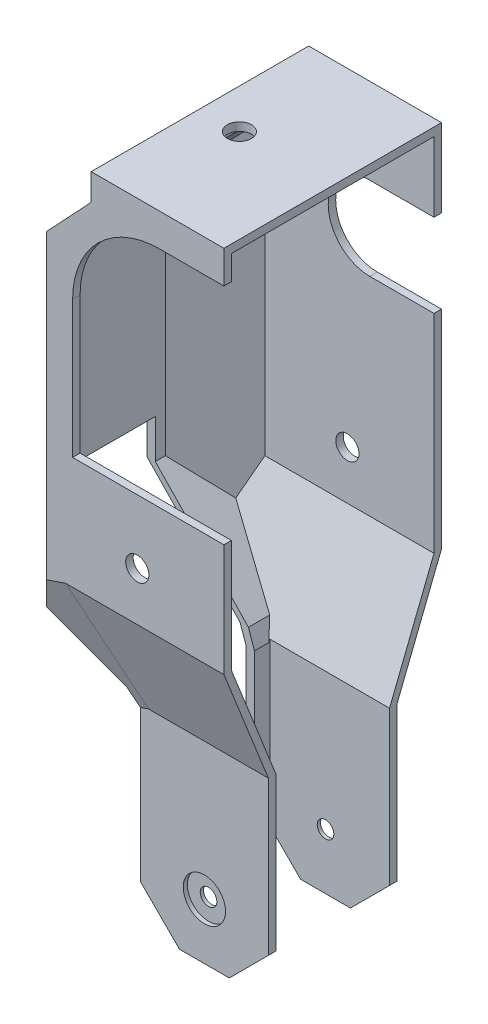
SolidWorks part; units mm, degrees
ref_plane "前视基准面" through (0, 0, 0) normal (0, 0, 1) x (1, 0, 0)
ref_plane "上视基准面" through (0, 0, 0) normal (0, 1, 0) x (1, 0, 0)
ref_plane "右视基准面" through (0, 0, 0) normal (1, 0, 0) x (0, 0, -1)
other "Configuration Table"
sketch "草图1" plane through (0, 0, 0) normal (0, 0, 1) x (1, 0, 0)
  line L0 (2.305, 31.67) -> (9.04, 31.67)
  line L1 (2.305, 21.64) -> (9.04, 21.64)
  line L8 (-9.04, 33.15) -> (-9.04, -3.4)
  line L9 (-9.04, -3.4) -> (9.04, -3.4)
  line L10 (9.04, -3.4) -> (9.04, 6.6704)
  line L11 (9.04, 6.6704) -> (9.04, 29.5296)
  line L12 (9.04, 29.5296) -> (9.04, 40.1)
  line L13 (9.04, 40.1) -> (-4.96, 40.1)
  line L14 (-4.96, 40.1) -> (-4.96, 37.5)
  line L15 (-4.96, 37.5) -> (-9.04, 33.15)
  line L16 (-9.04, 33.15) -> (-9.04, -3.4)
  line L17 (-9.04, -3.4) -> (9.04, -3.4)
  line L18 (9.04, -3.4) -> (9.04, 6.6704)
  line L19 (9.04, 6.6704) -> (9.04, 29.5296)
  line L20 (9.04, 29.5296) -> (9.04, 40.1)
  line L21 (9.04, 40.1) -> (-4.96, 40.1)
  line L22 (-4.96, 40.1) -> (-4.96, 37.5)
  line L23 (-4.96, 37.5) -> (-9.04, 33.15)
  circle A0 centre (2.305, 26.655) radius 5.015
  circle A1 centre (2.305, 26.655) radius 4.815
  circle A2 centre (2.305, 26.655) radius 4.815
  dimension "D1" = 0
  dimension "D2" = 0
  dimension "D3" = 0.2
extrude "凸台-拉伸1" add sketch "草图1" along normal blind 1 contours A0 L0 L20 L21 L22 L23 L16 L17 L18 L19 L1
sketch "草图2" plane through (0, 40.1, 0) normal (0, 1, 0) x (1, 0, 0)
  line L4 (9.04, 0) -> (-4.96, 0)
  line L5 (-4.96, 0) -> (-4.96, -1)
  line L6 (-4.96, -1) -> (9.04, -1)
  line L7 (9.04, -1) -> (9.04, 0)
  line L8 (9.04, 0) -> (-4.96, 0)
  line L9 (-4.96, 0) -> (-4.96, -1)
  line L10 (-4.96, -1) -> (9.04, -1)
  line L11 (9.04, -1) -> (9.04, 0)
  line L12 (9.04, 24.22) -> (-4.96, 24.22)
  line L13 (-4.96, 24.22) -> (-4.96, 0)
  line L14 (-4.96, 0) -> (9.04, 0)
  line L15 (9.04, 0) -> (9.04, 24.22)
  line L16 (9.04, 24.22) -> (-4.96, 24.22)
  line L17 (-4.96, 24.22) -> (-4.96, 0)
  line L18 (-4.96, 0) -> (9.04, 0)
  line L19 (9.04, 0) -> (9.04, 24.22)
  circle A0 centre (-1.2, 12.11) radius 1.45 construction
  circle A1 centre (-1.2, 12.11) radius 1.45
  line M10 (9.04, 0) -> (-4.96, 0)
  line M11 (-4.96, 0) -> (-4.96, -1)
  line M12 (-4.96, -1) -> (9.04, -1)
  line M13 (9.04, -1) -> (9.04, 0)
  dimension "D1" = 0
  dimension "D2" = 0
extrude "凸台-拉伸2" add sketch "草图2" along normal blind 1 contours L19 L16 L17 A1 M10 | M13 M10 M11 M12
sketch "草图3" plane through (0, 0, 1) normal (0, 0, 1) x (1, 0, 0)
  line L9 (2.305, 31.67) -> (9.04, 31.67)
  line L10 (9.04, 31.67) -> (9.04, 41.1)
  line L11 (9.04, 41.1) -> (-4.96, 41.1)
  line L12 (-4.96, 41.1) -> (-4.96, 37.5)
  line L13 (-4.96, 37.5) -> (-9.04, 33.15)
  line L14 (-9.04, 33.15) -> (-9.04, -3.4)
  line L15 (-9.04, -3.4) -> (9.04, -3.4)
  line L16 (9.04, -3.4) -> (9.04, 21.64)
  line L17 (9.04, 21.64) -> (2.305, 21.64)
  line L18 (2.305, 31.67) -> (9.04, 31.67)
  line L19 (9.04, 31.67) -> (9.04, 41.1)
  line L20 (9.04, 41.1) -> (-4.96, 41.1)
  line L21 (-4.96, 41.1) -> (-4.96, 37.5)
  line L22 (-4.96, 37.5) -> (-9.04, 33.15)
  line L23 (-9.04, 33.15) -> (-9.04, -3.4)
  line L24 (-9.04, -3.4) -> (9.04, -3.4)
  line L25 (9.04, -3.4) -> (9.04, 21.64)
  line L26 (9.04, 21.64) -> (2.305, 21.64)
  circle A0 centre (1, 2.46) radius 1.4 construction
  arc A1 (2.305, 31.67) -> (2.305, 21.64) centre (2.305, 26.655) ccw
  arc A2 (2.305, 31.67) -> (2.305, 21.64) centre (2.305, 26.655) ccw
  circle A3 centre (1, 2.46) radius 1.4
  dimension "D1" = 0
extrude "切除-拉伸1" cut sketch "草图3" against normal through all contours A3
sketch "草图4" plane through (0, 0, 1) normal (0, 0, 1) x (1, 0, 0)
  line L0 (-5.96, 41.1) -> (-5.96, 37.8956)
  line L1 (-5.96, 37.8956) -> (-9.7694, 33.8341)
  line L2 (-4.96, 41.1) -> (-5.96, 41.1)
  line L3 (-9.7694, 33.8341) -> (-17.34, 25.7625)
  line L4 (-15.94, 24.2) -> (-15.94, 27.2551)
  line L5 (-16.34, 24.2) -> (-16.34, 1.3)
  line L6 (-9.04, 1.3) -> (-9.04, 24.2)
  line L7 (-9.04, 24.2) -> (-15.94, 24.2)
  line L8 (-15.94, 24.2) -> (-15.94, 1.3)
  line L9 (2.305, 31.67) -> (9.04, 31.67)
  line L10 (9.04, 31.67) -> (9.04, 41.1)
  line L11 (9.04, 41.1) -> (-4.96, 41.1)
  line L12 (-4.96, 41.1) -> (-4.96, 37.5)
  line L13 (-4.96, 37.5) -> (-9.04, 33.15)
  line L14 (-9.04, 33.15) -> (-9.04, -3.4)
  line L15 (-9.04, -3.4) -> (9.04, -3.4)
  line L16 (9.04, -3.4) -> (9.04, 21.64)
  line L17 (9.04, 21.64) -> (2.305, 21.64)
  line L18 (2.305, 31.67) -> (9.04, 31.67)
  line L19 (9.04, 31.67) -> (9.04, 41.1)
  line L20 (9.04, 41.1) -> (-4.96, 41.1)
  line L21 (-4.96, 41.1) -> (-4.96, 37.5)
  line L22 (-4.96, 37.5) -> (-9.04, 33.15)
  line L23 (-9.04, 33.15) -> (-9.04, -3.4)
  line L24 (-9.04, -3.4) -> (9.04, -3.4)
  line L25 (9.04, -3.4) -> (9.04, 21.64)
  line L26 (9.04, 21.64) -> (2.305, 21.64)
  line L27 (-15.94, 1.3) -> (-9.04, 1.3)
  line L28 (-9.04, 1.3) -> (-9.04, 24.2)
  line L29 (-9.04, 24.2) -> (-15.94, 24.2)
  line L30 (-15.94, 24.2) -> (-15.94, 1.3)
  line L31 (-15.94, 1.3) -> (-9.04, 1.3)
  line L32 (-17.34, 24.2) -> (-17.34, 1.3)
  line L33 (-17.34, 24.2) -> (-17.34, 25.7625)
  line L34 (-17.34, 1.3) -> (-16.34, 1.3)
  line L35 (-9.04, 33.15) -> (-17.34, 24.3007)
  line L36 (-16.34, 24.2) -> (-16.34, 25.3669)
  line L37 (-16.34, 1.3) -> (-15.94, 1.3)
  arc A1 (2.305, 31.67) -> (2.305, 21.64) centre (2.305, 26.655) ccw
  arc A2 (2.305, 31.67) -> (2.305, 21.64) centre (2.305, 26.655) ccw
  line M25 (-4.96, 41.1) -> (-4.96, 37.5)
  line M26 (-4.96, 37.5) -> (-9.04, 33.15)
  dimension "D1" = 0
  dimension "D2" = 1
  dimension "D3" = 0
  dimension "D4" = 0.4
  dimension "D5" = 1
extrude "凸台-拉伸3" add sketch "草图4" against normal up to surface (25.22 mm away) contours L35 L4 L3 L33 | L5 L36 L35 L33 L32 L34 | L35 L2 L0 L1 L3 L4 M26 M25
sketch "草图5" plane through (0, 0, 1) normal (0, 0, 1) x (1, 0, 0)
  line L0 (-16.34, 1.3) -> (-9.04, 1.3)
  line L1 (-15.94, 1.3) -> (-9.04, 1.3) construction
  line L13 (2.305, 31.67) -> (9.04, 31.67)
  line L14 (9.04, 31.67) -> (9.04, 41.1)
  line L15 (9.04, 41.1) -> (-5.96, 41.1)
  line L16 (-5.96, 41.1) -> (-5.96, 37.8956)
  line L17 (-5.96, 37.8956) -> (-17.34, 25.7625)
  line L18 (-17.34, 25.7625) -> (-17.34, 1.3)
  line L19 (-17.34, 1.3) -> (-16.34, 1.3)
  line L20 (-16.34, 1.3) -> (-16.34, 25.3669)
  line L21 (-16.34, 25.3669) -> (-9.04, 33.15)
  line L22 (-9.04, 33.15) -> (-9.04, -3.4)
  line L23 (-9.04, -3.4) -> (9.04, -3.4)
  line L24 (9.04, -3.4) -> (9.04, 21.64)
  line L25 (9.04, 21.64) -> (2.305, 21.64)
  line L26 (2.305, 31.67) -> (9.04, 31.67)
  line L27 (9.04, 31.67) -> (9.04, 41.1)
  line L28 (9.04, 41.1) -> (-5.96, 41.1)
  line L29 (-5.96, 41.1) -> (-5.96, 37.8956)
  line L30 (-5.96, 37.8956) -> (-17.34, 25.7625)
  line L31 (-17.34, 25.7625) -> (-17.34, 1.3)
  line L32 (-17.34, 1.3) -> (-16.34, 1.3)
  line L33 (-16.34, 1.3) -> (-16.34, 25.3669)
  line L34 (-16.34, 25.3669) -> (-9.04, 33.15)
  line L35 (-9.04, 33.15) -> (-9.04, -3.4)
  line L36 (-9.04, -3.4) -> (9.04, -3.4)
  line L37 (9.04, -3.4) -> (9.04, 21.64)
  line L38 (9.04, 21.64) -> (2.305, 21.64)
  arc A1 (2.305, 31.67) -> (2.305, 21.64) centre (2.305, 26.655) ccw
  arc A2 (2.305, 31.67) -> (2.305, 21.64) centre (2.305, 26.655) ccw
  line M25 (-16.34, 1.3) -> (-16.34, 25.3669)
  line M26 (-16.34, 25.3669) -> (-9.04, 33.15)
  line M27 (-9.04, 33.15) -> (-9.04, -3.4)
  dimension "D1" = 0
extrude "凸台-拉伸4" add sketch "草图5" against normal blind 1 contours L0 M25 M27 M26
sketch "草图6" plane through (0, 0, 0) normal (0, 0, -1) x (-1, 0, 0)
  line L11 (-2.305, 21.64) -> (-9.04, 21.64)
  line L12 (-9.04, 21.64) -> (-9.04, -3.4)
  line L13 (-9.04, -3.4) -> (9.04, -3.4)
  line L14 (9.04, -3.4) -> (9.04, 1.3)
  line L15 (9.04, 1.3) -> (16.34, 1.3)
  line L16 (16.34, 1.3) -> (16.34, 25.3669)
  line L17 (16.34, 25.3669) -> (4.96, 37.5)
  line L18 (4.96, 37.5) -> (4.96, 40.1)
  line L19 (4.96, 40.1) -> (-9.04, 40.1)
  line L20 (-9.04, 40.1) -> (-9.04, 31.67)
  line L21 (-9.04, 31.67) -> (-2.305, 31.67)
  line L22 (-2.305, 21.64) -> (-9.04, 21.64)
  line L23 (-9.04, 21.64) -> (-9.04, -3.4)
  line L24 (-9.04, -3.4) -> (9.04, -3.4)
  line L25 (9.04, -3.4) -> (9.04, 1.3)
  line L26 (9.04, 1.3) -> (16.34, 1.3)
  line L27 (16.34, 1.3) -> (16.34, 25.3669)
  line L28 (16.34, 25.3669) -> (4.96, 37.5)
  line L29 (4.96, 37.5) -> (4.96, 40.1)
  line L30 (4.96, 40.1) -> (-9.04, 40.1)
  line L31 (-9.04, 40.1) -> (-9.04, 31.67)
  line L32 (-9.04, 31.67) -> (-2.305, 31.67)
  arc A1 (-2.305, 21.64) -> (-2.305, 31.67) centre (-2.305, 26.655) ccw
  arc A2 (-2.305, 21.64) -> (-2.305, 31.67) centre (-2.305, 26.655) ccw
  dimension "D1" = 0
extrude "切除-拉伸2" cut sketch "草图6" against normal blind 0.1
sketch "草图7" plane through (9.04, 0, 0) normal (1, 0, 0) x (0, 0, -1)
  line L0 (-0.1, -3.4) -> (5.26, -16.885)
  line L1 (-1, -3.4) -> (4.36, -16.885)
  line L2 (4.36, -16.885) -> (5.26, -16.885)
  line L3 (5.36, -16.885) -> (5.26, -16.885)
  line L4 (-0.1, -3.4) -> (-0.1, 21.64)
  line L5 (-0.1, 21.64) -> (-1, 21.64)
  line L6 (-1, 21.64) -> (-1, -3.4)
  line L7 (-1, -3.4) -> (-0.1, -3.4)
  line L8 (-0.1, -3.4) -> (-0.1, 21.64)
  line L9 (-0.1, 21.64) -> (-1, 21.64)
  line L10 (-1, 21.64) -> (-1, -3.4)
  line L11 (-1, -3.4) -> (-0.1, -3.4)
  line L32 (12.92, 35.35) -> (12.92, 21.71)
  line L33 (12.92, 14.49) -> (12.92, 0.85)
  line L34 (0, 6.6704) -> (0, -3.4)
  line L35 (0, -3.4) -> (5.36, -16.885)
  line L36 (5.36, -16.885) -> (5.36, -33.385)
  line L37 (5.36, -33.385) -> (7.36, -33.385)
  line L38 (7.36, -33.385) -> (7.36, -16.5021)
  line L39 (7.36, -16.5021) -> (2, -3.0171)
  line L40 (2, -3.0171) -> (2, 2.247)
  line L41 (14.92, -1.0458) -> (14.92, 1.3)
  line L42 (14.92, 1.3) -> (18.36, 1.3)
  line L43 (18.36, 1.3) -> (18.36, 24.2)
  line L44 (18.36, 24.2) -> (14.92, 24.2)
  line L45 (14.92, 24.2) -> (14.92, 38.1)
  line L46 (14.92, 38.1) -> (22.22, 38.1)
  line L47 (22.22, 38.1) -> (22.22, -3.0171)
  line L48 (22.22, -3.0171) -> (16.86, -16.5021)
  line L49 (16.86, -16.5021) -> (16.86, -33.385)
  line L50 (16.86, -33.385) -> (18.86, -33.385)
  line L51 (18.86, -33.385) -> (18.86, -16.885)
  line L52 (18.86, -16.885) -> (24.22, -3.4)
  line L53 (24.22, -3.4) -> (24.22, 40.1)
  line L54 (24.22, 40.1) -> (0, 40.1)
  line L55 (0, 40.1) -> (0, 29.5296)
  line L56 (12.92, 35.35) -> (12.92, 21.71)
  line L57 (12.92, 14.49) -> (12.92, 0.85)
  line L58 (0, 6.6704) -> (0, -3.4)
  line L59 (0, -3.4) -> (5.36, -16.885)
  line L60 (5.36, -16.885) -> (5.36, -33.385)
  line L61 (5.36, -33.385) -> (7.36, -33.385)
  line L62 (7.36, -33.385) -> (7.36, -16.5021)
  line L63 (7.36, -16.5021) -> (2, -3.0171)
  line L64 (2, -3.0171) -> (2, 2.247)
  line L65 (14.92, -1.0458) -> (14.92, 1.3)
  line L66 (14.92, 1.3) -> (18.36, 1.3)
  line L67 (18.36, 1.3) -> (18.36, 24.2)
  line L68 (18.36, 24.2) -> (14.92, 24.2)
  line L69 (14.92, 24.2) -> (14.92, 38.1)
  line L70 (14.92, 38.1) -> (22.22, 38.1)
  line L71 (22.22, 38.1) -> (22.22, -3.0171)
  line L72 (22.22, -3.0171) -> (16.86, -16.5021)
  line L73 (16.86, -16.5021) -> (16.86, -33.385)
  line L74 (16.86, -33.385) -> (18.86, -33.385)
  line L75 (18.86, -33.385) -> (18.86, -16.885)
  line L76 (18.86, -16.885) -> (24.22, -3.4)
  line L77 (24.22, -3.4) -> (24.22, 40.1)
  line L78 (24.22, 40.1) -> (0, 40.1)
  line L79 (0, 40.1) -> (0, 29.5296)
  arc A4 (12.92, 14.49) -> (12.92, 21.71) centre (12.92, 18.1) ccw
  arc A5 (0, 6.6704) -> (12.92, 0.85) centre (12.92, 18.1) ccw
  arc A6 (2, 2.247) -> (14.92, -1.0458) centre (12.92, 18.1) ccw
  arc A7 (12.92, 35.35) -> (0, 29.5296) centre (12.92, 18.1) ccw
  arc A8 (12.92, 14.49) -> (12.92, 21.71) centre (12.92, 18.1) ccw
  arc A9 (0, 6.6704) -> (12.92, 0.85) centre (12.92, 18.1) ccw
  arc A10 (2, 2.247) -> (14.92, -1.0458) centre (12.92, 18.1) ccw
  arc A11 (12.92, 35.35) -> (0, 29.5296) centre (12.92, 18.1) ccw
  line M38 (-1, -3.4) -> (-0.1, -3.4)
  dimension "D1" = 0
  dimension "D2" = 0
extrude "凸台-拉伸5" add sketch "草图7" against normal up to surface (18.08 mm away) contours L1 L2 L0 M38
sketch "草图8" plane through (0, 1.3, 0) normal (0, -1, 0) x (1, 0, 0)
  line L6 (-16.34, -24.22) -> (-16.34, 0.1)
  line L7 (-16.34, 0.1) -> (-9.04, 0.1)
  line L8 (-9.04, 0.1) -> (-9.04, 1)
  line L9 (-9.04, 1) -> (-17.34, 1)
  line L10 (-17.34, 1) -> (-17.34, -24.22)
  line L11 (-17.34, -24.22) -> (-16.34, -24.22)
  line L12 (-16.34, -24.22) -> (-16.34, 0.1)
  line L13 (-16.34, 0.1) -> (-9.04, 0.1)
  line L14 (-9.04, 0.1) -> (-9.04, 1)
  line L15 (-9.04, 1) -> (-17.34, 1)
  line L16 (-17.34, 1) -> (-17.34, -24.22)
  line L17 (-17.34, -24.22) -> (-16.34, -24.22)
  dimension "D1" = 0
extrude "凸台-拉伸6" add sketch "草图8" along normal up to vertex (4.7 mm away) up to point (-9.04, -3.4, 1)
sketch "草图9" plane through (0, 0, 1) normal (0, 0, 1) x (1, 0, 0)
  line L0 (-17.34, -3.4) -> (-4.39, -16.885)
  line L1 (-4.39, -16.885) -> (-9.04, -3.4)
  line L10 (-17.34, -3.4) -> (-9.04, -3.4)
  line L11 (-9.04, -3.4) -> (9.04, -3.4)
  line L12 (9.04, -3.4) -> (9.04, 21.64)
  line L13 (9.04, 21.64) -> (2.305, 21.64)
  line L14 (2.305, 31.67) -> (9.04, 31.67)
  line L15 (9.04, 31.67) -> (9.04, 41.1)
  line L16 (9.04, 41.1) -> (-5.96, 41.1)
  line L17 (-5.96, 41.1) -> (-5.96, 37.8956)
  line L18 (-5.96, 37.8956) -> (-17.34, 25.7625)
  line L19 (-17.34, 25.7625) -> (-17.34, -3.4)
  line L20 (-17.34, -3.4) -> (-9.04, -3.4)
  line L21 (-9.04, -3.4) -> (9.04, -3.4)
  line L22 (9.04, -3.4) -> (9.04, 21.64)
  line L23 (9.04, 21.64) -> (2.305, 21.64)
  line L24 (2.305, 31.67) -> (9.04, 31.67)
  line L25 (9.04, 31.67) -> (9.04, 41.1)
  line L26 (9.04, 41.1) -> (-5.96, 41.1)
  line L27 (-5.96, 41.1) -> (-5.96, 37.8956)
  line L28 (-5.96, 37.8956) -> (-17.34, 25.7625)
  line L29 (-17.34, 25.7625) -> (-17.34, -3.4)
  arc A1 (2.305, 31.67) -> (2.305, 21.64) centre (2.305, 26.655) ccw
  arc A2 (2.305, 31.67) -> (2.305, 21.64) centre (2.305, 26.655) ccw
  line M14 (-17.34, -3.4) -> (-9.04, -3.4)
  dimension "D1" = 0
extrude "凸台-拉伸7" add sketch "草图9" against normal up to vertex (6.26 mm away) contours L0 L1 M14 up to point (-4.39, -16.885, -5.26)
sketch "草图10" plane through (-9.1271, -3.1473, 0) normal (0.9454, 0.326, 0) x (0, 0, -1)
  line L3 (-1, -14.5315) -> (4.36, -14.5315)
  line L4 (4.36, -14.5315) -> (-1, -0.2673)
  line L5 (-1, -0.2673) -> (-1, -14.5315)
  line L6 (-1, -14.5315) -> (4.36, -14.5315)
  line L7 (4.36, -14.5315) -> (-1, -0.2673)
  line L8 (-1, -0.2673) -> (-1, -14.5315)
  dimension "D1" = 0
extrude "切除-拉伸3" cut sketch "草图10" against normal through all
sketch "草图11" plane through (0, 0, -5.26) normal (0, 0, -1) x (-1, 0, 0)
  line L4 (4.39, -16.885) -> (17.34, -3.4)
  line L5 (17.34, -3.4) -> (16.34, -3.4)
  line L6 (16.34, -3.4) -> (9.04, -3.4)
  line L7 (9.04, -3.4) -> (4.39, -16.885)
  line L8 (4.39, -16.885) -> (17.34, -3.4)
  line L9 (17.34, -3.4) -> (16.34, -3.4)
  line L10 (16.34, -3.4) -> (9.04, -3.4)
  line L11 (9.04, -3.4) -> (4.39, -16.885)
  dimension "D1" = 0
extrude "切除-拉伸4" cut sketch "草图11" against normal up to surface (5.36 mm away)
sketch "草图13" plane through (0, 0, -24.22) normal (0, 0, -1) x (-1, 0, 0)
  line L0 (16.34, -3.4) -> (3.39, -16.885)
  line L5 (-9.04, -16.885) -> (4.39, -16.885)
  line L6 (4.39, -16.885) -> (17.34, -3.4)
  line L7 (17.34, -3.4) -> (16.34, -3.4)
  line L8 (16.34, -3.4) -> (-9.04, -3.4)
  line L9 (-9.04, -3.4) -> (-9.04, -16.885)
  line L10 (-9.04, 40.1) -> (4.96, 40.1)
  line L11 (4.96, 40.1) -> (4.96, 37.5)
  line L12 (4.96, 37.5) -> (16.34, 25.3669)
  line L13 (16.34, 25.3669) -> (16.34, -3.4)
  line L14 (16.34, -3.4) -> (17.34, -3.4)
  line L15 (17.34, -3.4) -> (17.34, 25.7625)
  line L16 (17.34, 25.7625) -> (5.96, 37.8956)
  line L17 (5.96, 37.8956) -> (5.96, 41.1)
  line L18 (5.96, 41.1) -> (-9.04, 41.1)
  line L19 (-9.04, 41.1) -> (-9.04, 40.1)
  line L20 (-9.04, 40.1) -> (4.96, 40.1)
  line L21 (4.96, 40.1) -> (4.96, 37.5)
  line L22 (4.96, 37.5) -> (16.34, 25.3669)
  line L23 (16.34, 25.3669) -> (16.34, -3.4)
  line L24 (16.34, -3.4) -> (17.34, -3.4)
  line L25 (17.34, -3.4) -> (17.34, 25.7625)
  line L26 (17.34, 25.7625) -> (5.96, 37.8956)
  line L27 (5.96, 37.8956) -> (5.96, 41.1)
  line L28 (5.96, 41.1) -> (-9.04, 41.1)
  line L29 (-9.04, 41.1) -> (-9.04, 40.1)
  line L30 (-9.04, -16.885) -> (4.39, -16.885)
  line L31 (4.39, -16.885) -> (17.34, -3.4)
  line L32 (17.34, -3.4) -> (16.34, -3.4)
  line L33 (16.34, -3.4) -> (-9.04, -3.4)
  line L34 (-9.04, -3.4) -> (-9.04, -16.885)
  line M21 (16.34, -3.4) -> (17.34, -3.4)
  dimension "D1" = 0
  dimension "D2" = 0
extrude "凸台-拉伸8" add sketch "草图13" against normal up to surface (26.1142 mm away) contours L30 L31 L0 M21
sketch "草图14" plane through (-10.1992, -9.7945, 0) normal (0.7213, 0.6927, 0) x (0, 0, -1)
  line L3 (-1.8942, 8.8657) -> (-1, 6.2438)
  line L4 (-1, 6.2438) -> (-1, 8.8657)
  line L5 (-1, 8.8657) -> (-1.8942, 8.8657)
  line L6 (-1.8942, 8.8657) -> (-1, 6.2438)
  line L7 (-1, 6.2438) -> (-1, 8.8657)
  line L8 (-1, 8.8657) -> (-1.8942, 8.8657)
  line L10 (-1, 8.8657) -> (-1, 9.5583)
  line L11 (-1, 9.5583) -> (-2.0167, 9.5583)
  line L12 (-2.0167, 9.5583) -> (-1.8942, 8.8657)
  line L13 (-1.8942, 8.8657) -> (-1, 8.8657)
  line L14 (-1, 8.8657) -> (-1, 9.5583)
  line L15 (-1, 9.5583) -> (-2.0167, 9.5583)
  line L16 (-2.0167, 9.5583) -> (-1.8942, 8.8657)
  line L17 (-1.8942, 8.8657) -> (-1, 8.8657)
  line M4 (-1.8942, 8.8657) -> (-1, 6.2438)
  line M5 (-1, 6.2438) -> (-1, 8.8657)
  line M6 (-1, 8.8657) -> (-1.8942, 8.8657)
  dimension "D1" = 0
  dimension "D2" = 0
extrude "切除-拉伸6" cut sketch "草图14" against normal up to surface (0.7213 mm away) contours L15 L16 L14 M6 | M6 M4 M5 up to face at (-12.16, -8.794, -9.9567)
sketch "草图15" plane through (0, 0, -5.36) normal (0, 0, 1) x (1, 0, 0)
  line L3 (9.04, -33.385) -> (9.04, -16.885)
  line L4 (9.04, -16.885) -> (-4.39, -16.885)
  line L5 (-4.39, -16.885) -> (-4.39, -33.385)
  line L6 (9.04, -33.385) -> (9.04, -16.885)
  line L7 (9.04, -16.885) -> (-4.39, -16.885)
  line L8 (-4.39, -16.885) -> (-4.39, -33.385)
  circle A0 centre (2.325, -33.385) radius 1 construction
  arc A1 (-4.39, -33.385) -> (9.04, -33.385) centre (2.325, -33.385) ccw
  arc A2 (-4.39, -33.385) -> (9.04, -33.385) centre (2.325, -33.385) ccw
  circle A3 centre (2.325, -33.385) radius 1
  dimension "D1" = 0
extrude "凸台-拉伸9" add sketch "草图15" along normal up to vertex (1 mm away)
sketch "草图16" plane through (0, 0, -4.36) normal (0, 0, 1) x (1, 0, 0)
  line L0 (-0.675, -40.1) -> (5.325, -40.1)
  line L1 (-4.39, -33.385) -> (-4.39, -36.385)
  line L2 (-4.39, -36.385) -> (-0.675, -40.1)
  line L3 (9.04, -33.385) -> (9.04, -16.885)
  line L4 (9.04, -16.885) -> (-4.39, -16.885)
  line L5 (-4.39, -16.885) -> (-4.39, -33.385)
  line L6 (9.04, -33.385) -> (9.04, -16.885)
  line L7 (9.04, -16.885) -> (-4.39, -16.885)
  line L8 (-4.39, -16.885) -> (-4.39, -33.385)
  line L9 (9.04, -33.385) -> (9.04, -36.385)
  line L10 (9.04, -36.385) -> (5.325, -40.1)
  arc A1 (-4.39, -33.385) -> (9.04, -33.385) centre (2.325, -33.385) ccw
  arc A2 (-4.39, -33.385) -> (9.04, -33.385) centre (2.325, -33.385) ccw
  point P8 (2.325, -40.1)
  dimension "D2" = 6
  dimension "D3" = 3
  dimension "D4" = 3
  dimension "D1" = 0
extrude "凸台-拉伸10" add sketch "草图16" against normal up to vertex (1 mm away) contours L10 L9 L1 L0 | L1 L2 L0
sketch "草图17" plane through (0, 0, -5.36) normal (0, 0, -1) x (-1, 0, 0)
  line L7 (-5.325, -40.1) -> (0.675, -40.1)
  line L8 (0.675, -40.1) -> (4.39, -36.385)
  line L9 (4.39, -36.385) -> (4.39, -16.885)
  line L10 (4.39, -16.885) -> (3.39, -16.885)
  line L11 (3.39, -16.885) -> (-9.04, -16.885)
  line L12 (-9.04, -16.885) -> (-9.04, -36.385)
  line L13 (-9.04, -36.385) -> (-5.325, -40.1)
  line L14 (-5.325, -40.1) -> (0.675, -40.1)
  line L15 (0.675, -40.1) -> (4.39, -36.385)
  line L16 (4.39, -36.385) -> (4.39, -16.885)
  line L17 (4.39, -16.885) -> (3.39, -16.885)
  line L18 (3.39, -16.885) -> (-9.04, -16.885)
  line L19 (-9.04, -16.885) -> (-9.04, -36.385)
  line L20 (-9.04, -36.385) -> (-5.325, -40.1)
  dimension "D1" = 0
extrude "切除-拉伸7" cut sketch "草图17" against normal blind 0.1
sketch "草图18" plane through (-17.34, 0, 0) normal (-1, 0, 0) x (0, 0, 1)
  line L0 (-16.86, -16.5021) -> (-22.0678, -3.4) construction
  line L1 (-16.86, -16.5021) -> (-22.0678, -3.4)
  line L2 (-16.86, -16.5021) -> (-16.7078, -16.885)
  line L3 (-24.22, -3.4) -> (-18.86, -16.885) construction
  line L4 (1, 25.7625) -> (-24.22, 25.7625)
  line L5 (-24.22, 25.7625) -> (-24.22, -3.4)
  line L6 (-24.22, -3.4) -> (1, -3.4)
  line L7 (1, -3.4) -> (1, 25.7625)
  line L8 (1, 25.7625) -> (-24.22, 25.7625)
  line L9 (-24.22, 25.7625) -> (-24.22, -3.4)
  line L10 (-24.22, -3.4) -> (1, -3.4)
  line L11 (1, -3.4) -> (1, 25.7625)
  line L12 (-24.22, -3.4) -> (-18.86, -16.885)
  line L14 (1, -5.5501) -> (1, -3.4)
  line L15 (1, -3.4) -> (-24.22, -3.4)
  line L16 (-24.22, -3.4) -> (-24.22, -16.885)
  line L17 (-24.22, -16.885) -> (-5.26, -16.885)
  line L18 (-5.26, -16.885) -> (-4.36, -16.885)
  line L19 (-4.36, -16.885) -> (1, -5.5501)
  line L20 (1, -5.5501) -> (1, -3.4)
  line L21 (1, -3.4) -> (-24.22, -3.4)
  line L22 (-24.22, -3.4) -> (-24.22, -16.885)
  line L23 (-24.22, -16.885) -> (-5.26, -16.885)
  line L24 (-5.26, -16.885) -> (-4.36, -16.885)
  line L25 (-4.36, -16.885) -> (1, -5.5501)
  dimension "D1" = 0
  dimension "D2" = 0
extrude "切除-拉伸10" cut sketch "草图18" against normal up to surface (1 mm away) contours L22 L23 L12
sketch "草图20" plane through (-17.34, 0, 0) normal (-1, 0, 0) x (0, 0, 1)
  line L0 (-18.36, 1.3) -> (-18.36, 24.2) construction
  line L1 (-18.36, 1.3) -> (-18.36, 24.2)
  line L2 (-14.92, 1.3) -> (-18.36, 1.3) construction
  line L3 (-14.92, 1.3) -> (-18.36, 1.3)
  line L4 (1, 25.7625) -> (-24.22, 25.7625)
  line L5 (-24.22, 25.7625) -> (-24.22, -3.4)
  line L6 (-24.22, -3.4) -> (1, -3.4)
  line L7 (1, -3.4) -> (1, 25.7625)
  line L8 (1, 25.7625) -> (-24.22, 25.7625)
  line L9 (-24.22, 25.7625) -> (-24.22, -3.4)
  line L10 (-24.22, -3.4) -> (1, -3.4)
  line L11 (1, -3.4) -> (1, 25.7625)
  line L12 (-18.36, 24.2) -> (-14.92, 24.2) construction
  line L13 (-18.36, 24.2) -> (-14.92, 24.2)
  line L14 (1, -3.4) -> (-24.22, -3.4)
  line L15 (-24.22, -3.4) -> (-18.86, -16.885)
  line L16 (-18.86, -16.885) -> (-5.26, -16.885)
  line L17 (-5.26, -16.885) -> (-4.36, -16.885)
  line L18 (-4.36, -16.885) -> (1, -5.5501)
  line L19 (1, -5.5501) -> (1, -3.4)
  line L20 (1, -3.4) -> (-24.22, -3.4)
  line L21 (-24.22, -3.4) -> (-18.86, -16.885)
  line L22 (-18.86, -16.885) -> (-5.26, -16.885)
  line L23 (-5.26, -16.885) -> (-4.36, -16.885)
  line L24 (-4.36, -16.885) -> (1, -5.5501)
  line L25 (1, -5.5501) -> (1, -3.4)
  line L26 (-14.92, 24.2) -> (-6.46, 24.2) construction
  line L27 (-14.92, 24.2) -> (-6.46, 24.2)
  line L28 (-24.22, -3.4) -> (-16.11, -3.4)
  line L29 (-18.36, 1.3) -> (-6.46, 1.3)
  line L30 (-18.36, 1.3) -> (-18.36, 24.2)
  line L31 (-18.36, 24.2) -> (-6.46, 24.2)
  line L32 (-6.46, 1.3) -> (-6.46, 24.2)
  line L33 (-16.11, 1.3) -> (-7.11, 1.3)
  line L34 (-16.11, 1.3) -> (-16.11, -19.988)
  line L35 (-16.11, -19.988) -> (-7.11, -19.988)
  line L36 (-7.11, 1.3) -> (-7.11, -19.988)
  line L37 (-18.86, -16.885) -> (-16.11, -16.885)
  line L38 (-7.11, -16.885) -> (-4.36, -16.885)
  dimension "D3" = 9
  dimension "D4" = 2.75
  dimension "D1" = 0
  dimension "D2" = 0
extrude "切除-拉伸12" cut sketch "草图20" against normal blind 51.1 contours L36 L20 L34 L22 | L36 L22 L34 L35 | L36 L29 L3 L34 L20
sketch "草图22" plane through (0, 0, -4.36) normal (0, 0, 1) x (1, 0, 0)
  line L0 (-5.39, -16.885) -> (-5.39, -35.385)
  line L1 (-4.39, -36.385) -> (-5.39, -35.385)
  line L2 (-5.39, -16.885) -> (-5.39, -15.8437)
  line L3 (-5.39, -16.885) -> (-5.39, -36.385) construction
  line L5 (-9.04, -3.4) -> (-15.2752, -5.5501)
  line L6 (-4.39, -16.885) -> (-4.39, -36.385)
  line L7 (-4.39, -36.385) -> (-0.675, -40.1)
  line L8 (-0.675, -40.1) -> (5.325, -40.1)
  line L9 (5.325, -40.1) -> (9.04, -36.385)
  line L10 (9.04, -36.385) -> (9.04, -16.885)
  line L11 (9.04, -16.885) -> (-4.39, -16.885)
  line L12 (-4.39, -16.885) -> (-4.39, -36.385)
  line L13 (-4.39, -36.385) -> (-0.675, -40.1)
  line L14 (-0.675, -40.1) -> (5.325, -40.1)
  line L15 (5.325, -40.1) -> (9.04, -36.385)
  line L16 (9.04, -36.385) -> (9.04, -16.885)
  line L17 (9.04, -16.885) -> (-4.39, -16.885)
  line L18 (-15.2752, -5.5501) -> (-4.39, -16.885)
  line L19 (-4.39, -16.885) -> (-9.04, -3.4)
  line L20 (-9.04, -3.4) -> (-15.2752, -5.5501)
  line L21 (-15.2752, -5.5501) -> (-4.39, -16.885)
  line L22 (-4.39, -16.885) -> (-9.04, -3.4)
  line M11 (-4.39, -16.885) -> (-4.39, -36.385)
  dimension "D1" = 0
  dimension "D2" = 1
  dimension "D3" = 0
extrude "凸台-拉伸11" add sketch "草图22" against normal up to vertex contours L21 L2 L0 L1 M11
sketch "草图23" plane through (0, 0, -7.11) normal (0, 0, -1) x (-1, 0, 0)
  line L0 (4.39, -16.885) -> (4.9502, -15.2603)
  line L1 (9.04, -3.4) -> (4.39, -16.885) construction
  line L6 (17.34, -3.4) -> (16.34, -3.4)
  line L7 (16.34, -3.4) -> (3.39, -16.885)
  line L8 (3.39, -16.885) -> (4.39, -16.885)
  line L9 (17.34, -3.4) -> (17.34, 1.3)
  line L10 (17.34, 1.3) -> (16.34, 1.3)
  line L11 (16.34, 1.3) -> (16.34, -3.4)
  line L12 (16.34, -3.4) -> (3.39, -16.885)
  line L13 (3.39, -16.885) -> (4.39, -16.885)
  line L14 (4.39, -16.885) -> (4.39, -36.385)
  line L15 (4.39, -36.385) -> (5.39, -35.385)
  line L16 (5.39, -35.385) -> (5.39, -15.8437)
  line L17 (5.39, -15.8437) -> (17.34, -3.4)
  line L18 (17.34, -3.4) -> (17.34, 1.3)
  line L19 (17.34, 1.3) -> (16.34, 1.3)
  line L20 (16.34, 1.3) -> (16.34, -3.4)
  line L21 (16.34, -3.4) -> (3.39, -16.885)
  line L22 (3.39, -16.885) -> (4.39, -16.885)
  line L23 (4.39, -16.885) -> (4.39, -36.385)
  line L24 (4.39, -36.385) -> (5.39, -35.385)
  line L25 (5.39, -35.385) -> (5.39, -15.8437)
  line L26 (5.39, -15.8437) -> (17.34, -3.4)
  line L27 (4.39, -16.885) -> (17.34, -3.4)
  line L28 (17.34, -3.4) -> (16.34, -3.4)
  line L29 (16.34, -3.4) -> (3.39, -16.885)
  line L30 (3.39, -16.885) -> (4.39, -16.885)
  line L31 (4.39, -16.885) -> (17.34, -3.4)
  line M13 (16.34, -3.4) -> (3.39, -16.885)
  line M14 (3.39, -16.885) -> (4.39, -16.885)
  dimension "D1" = 0
  dimension "D2" = 0
extrude "切除-拉伸13" cut sketch "草图23" against normal up to surface (2.4958 mm away) contours L0 M14 M13
sketch "草图25" plane through (0, 0, -7.11) normal (0, 0, -1) x (-1, 0, 0)
  line L0 (5.0448, -15.2929) -> (4.4845, -16.9176)
  line L1 (4.4845, -16.9176) -> (4.39, -17.1918)
  line L2 (5.0448, -15.2929) -> (5.1153, -15.0884)
  line L9 (4.9502, -15.2603) -> (4.39, -16.885)
  line L10 (4.39, -16.885) -> (4.39, -36.385)
  line L11 (4.39, -36.385) -> (5.39, -35.385)
  line L12 (5.39, -35.385) -> (5.39, -15.8437)
  line L13 (5.39, -15.8437) -> (17.34, -3.4)
  line L14 (17.34, -3.4) -> (17.34, 1.3)
  line L15 (17.34, 1.3) -> (16.34, 1.3)
  line L16 (16.34, 1.3) -> (16.34, -3.4)
  line L17 (16.34, -3.4) -> (4.9502, -15.2603)
  line L18 (4.9502, -15.2603) -> (4.39, -16.885)
  line L19 (4.39, -16.885) -> (4.39, -36.385)
  line L20 (4.39, -36.385) -> (5.39, -35.385)
  line L21 (5.39, -35.385) -> (5.39, -15.8437)
  line L22 (5.39, -15.8437) -> (17.34, -3.4)
  line L23 (17.34, -3.4) -> (17.34, 1.3)
  line L24 (17.34, 1.3) -> (16.34, 1.3)
  line L25 (16.34, 1.3) -> (16.34, -3.4)
  line L26 (16.34, -3.4) -> (4.9502, -15.2603)
  line M12 (4.9502, -15.2603) -> (4.39, -16.885)
  line M13 (4.39, -16.885) -> (4.39, -36.385)
  line M20 (16.34, -3.4) -> (4.9502, -15.2603)
  dimension "D1" = 0
  dimension "D2" = 0.1
extrude "切除-拉伸14" cut sketch "草图25" against normal up to surface (1.85 mm away) contours L0 L2 L1 M20 M12 M13
sketch "草图26" plane through (0, 0, -7.11) normal (0, 0, -1) x (-1, 0, 0)
  line L0 (5.39, -17.1918) -> (6.1153, -15.0884)
  line L9 (16.34, -3.4) -> (5.1153, -15.0884)
  line L10 (5.1153, -15.0884) -> (4.39, -17.1918)
  line L11 (4.39, -17.1918) -> (4.39, -36.385)
  line L12 (4.39, -36.385) -> (5.39, -35.385)
  line L13 (5.39, -35.385) -> (5.39, -15.8437)
  line L14 (5.39, -15.8437) -> (17.34, -3.4)
  line L15 (17.34, -3.4) -> (17.34, 1.3)
  line L16 (17.34, 1.3) -> (16.34, 1.3)
  line L17 (16.34, 1.3) -> (16.34, -3.4)
  line L18 (16.34, -3.4) -> (5.1153, -15.0884)
  line L19 (5.1153, -15.0884) -> (4.39, -17.1918)
  line L20 (4.39, -17.1918) -> (4.39, -36.385)
  line L21 (4.39, -36.385) -> (5.39, -35.385)
  line L22 (5.39, -35.385) -> (5.39, -15.8437)
  line L23 (5.39, -15.8437) -> (17.34, -3.4)
  line L24 (17.34, -3.4) -> (17.34, 1.3)
  line L25 (17.34, 1.3) -> (16.34, 1.3)
  line L26 (16.34, 1.3) -> (16.34, -3.4)
  line M15 (5.39, -35.385) -> (5.39, -15.8437)
  line M16 (5.39, -15.8437) -> (17.34, -3.4)
  dimension "D1" = 0
extrude "凸台-拉伸12" add sketch "草图26" against normal up to surface (2.75 mm away) contours L0 M15 M16 up to face at (1.08, -28.7977, -4.36)
sketch "草图27" plane through (0, 0, -4.36) normal (0, 0, 1) x (1, 0, 0)
  line L0 (-4.39, -16.885) -> (-5.39, -17.1918)
  line L8 (9.04, -16.885) -> (-4.39, -16.885)
  line L9 (-4.39, -16.885) -> (-6.1153, -15.0884)
  line L10 (-6.1153, -15.0884) -> (-5.39, -17.1918)
  line L11 (-5.39, -17.1918) -> (-5.39, -35.385)
  line L12 (-5.39, -35.385) -> (-0.675, -40.1)
  line L13 (-0.675, -40.1) -> (5.325, -40.1)
  line L14 (5.325, -40.1) -> (9.04, -36.385)
  line L15 (9.04, -36.385) -> (9.04, -16.885)
  line L16 (9.04, -16.885) -> (-4.39, -16.885)
  line L17 (-4.39, -16.885) -> (-6.1153, -15.0884)
  line L18 (-6.1153, -15.0884) -> (-5.39, -17.1918)
  line L19 (-5.39, -17.1918) -> (-5.39, -35.385)
  line L20 (-5.39, -35.385) -> (-0.675, -40.1)
  line L21 (-0.675, -40.1) -> (5.325, -40.1)
  line L22 (5.325, -40.1) -> (9.04, -36.385)
  line L23 (9.04, -36.385) -> (9.04, -16.885)
  line M11 (-4.39, -16.885) -> (-6.1153, -15.0884)
  line M12 (-6.1153, -15.0884) -> (-5.39, -17.1918)
  dimension "D1" = 0
extrude "凸台-拉伸13" add sketch "草图27" along normal up to surface (0.8495 mm away) contours L0 M11 M12
sketch "草图28" plane through (0, 0, -16.11) normal (0, 0, 1) x (1, 0, 0)
  line L6 (-17.34, -3.4) -> (-4.39, -16.885)
  line L7 (-4.39, -16.885) -> (-3.39, -16.885)
  line L8 (-3.39, -16.885) -> (-16.34, -3.4)
  line L9 (-16.34, -3.4) -> (-16.34, 1.3)
  line L10 (-16.34, 1.3) -> (-17.34, 1.3)
  line L11 (-17.34, 1.3) -> (-17.34, -3.4)
  line L12 (-17.34, -3.4) -> (-4.39, -16.885)
  line L13 (-4.39, -16.885) -> (-3.39, -16.885)
  line L14 (-3.39, -16.885) -> (-16.34, -3.4)
  line L15 (-16.34, -3.4) -> (-16.34, 1.3)
  line L16 (-16.34, 1.3) -> (-17.34, 1.3)
  line L17 (-17.34, 1.3) -> (-17.34, -3.4)
  line L22 (-6.1153, -15.0884) -> (-5.39, -17.1918)
  line L23 (-17.34, -3.4) -> (-6.1153, -15.0884)
  line L24 (-17.34, 1.3) -> (-17.34, -3.4)
  line L25 (-16.34, 1.3) -> (-17.34, 1.3)
  line L26 (-16.34, -3.4) -> (-16.34, 1.3)
  line L27 (-5.1153, -15.0884) -> (-16.34, -3.4)
  line L28 (-4.39, -17.1918) -> (-5.1153, -15.0884)
  line L29 (-4.39, -36.385) -> (-4.39, -17.1918)
  line L30 (-5.39, -35.385) -> (-4.39, -36.385)
  line L31 (-5.39, -17.1918) -> (-5.39, -35.385)
  line L32 (-6.1153, -15.0884) -> (-5.39, -17.1918)
  line L33 (-17.34, -3.4) -> (-6.1153, -15.0884)
  line L34 (-17.34, 1.3) -> (-17.34, -3.4)
  line L35 (-16.34, 1.3) -> (-17.34, 1.3)
  line L36 (-16.34, -3.4) -> (-16.34, 1.3)
  line L37 (-5.1153, -15.0884) -> (-16.34, -3.4)
  line L38 (-4.39, -17.1918) -> (-5.1153, -15.0884)
  line L39 (-4.39, -36.385) -> (-4.39, -17.1918)
  line L40 (-5.39, -35.385) -> (-4.39, -36.385)
  line L41 (-5.39, -17.1918) -> (-5.39, -35.385)
  line M17 (-17.34, -3.4) -> (-4.39, -16.885)
  line M18 (-4.39, -16.885) -> (-3.39, -16.885)
  line M19 (-3.39, -16.885) -> (-16.34, -3.4)
  dimension "D1" = 0
  dimension "D2" = 0
extrude "切除-拉伸15" cut sketch "草图28" against normal up to surface (2.75 mm away) contours L38 M17 M18 M19
sketch "草图29" plane through (0, 0, -16.11) normal (0, 0, 1) x (1, 0, 0)
  line L6 (-4.555, -16.7131) -> (-5.1153, -15.0884)
  line L7 (-5.1153, -15.0884) -> (-16.34, -3.4)
  line L8 (-16.34, -3.4) -> (-16.34, 1.3)
  line L9 (-16.34, 1.3) -> (-17.34, 1.3)
  line L10 (-17.34, 1.3) -> (-17.34, -3.4)
  line L11 (-17.34, -3.4) -> (-4.555, -16.7131)
  line L12 (-4.555, -16.7131) -> (-5.1153, -15.0884)
  line L13 (-5.1153, -15.0884) -> (-16.34, -3.4)
  line L14 (-16.34, -3.4) -> (-16.34, 1.3)
  line L15 (-16.34, 1.3) -> (-17.34, 1.3)
  line L16 (-17.34, 1.3) -> (-17.34, -3.4)
  line L17 (-17.34, -3.4) -> (-4.555, -16.7131)
  line L22 (-6.1153, -15.0884) -> (-5.39, -17.1918)
  line L23 (-17.34, -3.4) -> (-6.1153, -15.0884)
  line L24 (-17.34, 1.3) -> (-17.34, -3.4)
  line L25 (-16.34, 1.3) -> (-17.34, 1.3)
  line L26 (-16.34, -3.4) -> (-16.34, 1.3)
  line L27 (-5.1153, -15.0884) -> (-16.34, -3.4)
  line L28 (-4.39, -17.1918) -> (-5.1153, -15.0884)
  line L29 (-4.39, -36.385) -> (-4.39, -17.1918)
  line L30 (-5.39, -35.385) -> (-4.39, -36.385)
  line L31 (-5.39, -17.1918) -> (-5.39, -35.385)
  line L32 (-6.1153, -15.0884) -> (-5.39, -17.1918)
  line L33 (-17.34, -3.4) -> (-6.1153, -15.0884)
  line L34 (-17.34, 1.3) -> (-17.34, -3.4)
  line L35 (-16.34, 1.3) -> (-17.34, 1.3)
  line L36 (-16.34, -3.4) -> (-16.34, 1.3)
  line L37 (-5.1153, -15.0884) -> (-16.34, -3.4)
  line L38 (-4.39, -17.1918) -> (-5.1153, -15.0884)
  line L39 (-4.39, -36.385) -> (-4.39, -17.1918)
  line L40 (-5.39, -35.385) -> (-4.39, -36.385)
  line L41 (-5.39, -17.1918) -> (-5.39, -35.385)
  dimension "D1" = 0
  dimension "D2" = 0
extrude "凸台-拉伸14" add sketch "草图29" against normal up to vertex (3.4641 mm away) contours L32 L41 L40 L39 L38 L17
sketch "草图30" plane through (0, 0, -16.11) normal (0, 0, 1) x (1, 0, 0)
  line L0 (-6.1153, -15.0884) -> (-5.1153, -15.0884)
  line L10 (-4.39, -17.1918) -> (-5.1153, -15.0884)
  line L11 (-5.1153, -15.0884) -> (-16.34, -3.4)
  line L12 (-16.34, -3.4) -> (-16.34, 1.3)
  line L13 (-16.34, 1.3) -> (-17.34, 1.3)
  line L14 (-17.34, 1.3) -> (-17.34, -3.4)
  line L15 (-17.34, -3.4) -> (-6.1153, -15.0884)
  line L16 (-6.1153, -15.0884) -> (-5.39, -17.1918)
  line L17 (-5.39, -17.1918) -> (-5.39, -35.385)
  line L18 (-5.39, -35.385) -> (-4.39, -36.385)
  line L19 (-4.39, -36.385) -> (-4.39, -17.1918)
  line L20 (-4.39, -17.1918) -> (-5.1153, -15.0884)
  line L21 (-5.1153, -15.0884) -> (-16.34, -3.4)
  line L22 (-16.34, -3.4) -> (-16.34, 1.3)
  line L23 (-16.34, 1.3) -> (-17.34, 1.3)
  line L24 (-17.34, 1.3) -> (-17.34, -3.4)
  line L25 (-17.34, -3.4) -> (-6.1153, -15.0884)
  line L26 (-6.1153, -15.0884) -> (-5.39, -17.1918)
  line L27 (-5.39, -17.1918) -> (-5.39, -35.385)
  line L28 (-5.39, -35.385) -> (-4.39, -36.385)
  line L29 (-4.39, -36.385) -> (-4.39, -17.1918)
  line M12 (-4.39, -17.1918) -> (-5.1153, -15.0884)
  line M18 (-6.1153, -15.0884) -> (-5.39, -17.1918)
  line M19 (-5.39, -17.1918) -> (-5.39, -35.385)
  line M20 (-5.39, -35.385) -> (-4.39, -36.385)
  line M21 (-4.39, -36.385) -> (-4.39, -17.1918)
  dimension "D1" = 0
extrude "切除-拉伸16" cut sketch "草图30" against normal up to surface (0.75 mm away) contours L0 M18 M19 M20 M21 M12
chamfer "倒角1" distance 0.8 angle 45 1 edges at (-5.6153, -15.0884, -16.11)
chamfer "倒角3" distance 6 angle 45 2 edges at (-17.34, 11.1812, 1) (-16.34, 10.9835, 0.1)
sketch "草图32" plane through (0, 0, -24.22) normal (0, 0, -1) x (-1, 0, 0)
  line L0 (16.34, -3.4) -> (10.34, -3.4)
  line L1 (10.34, -3.4) -> (10.34, 31.764)
  line L2 (10.54, -3.4) -> (10.54, 31.764)
  line L10 (16.34, -3.4) -> (17.34, -3.4)
  line L11 (17.34, -3.4) -> (17.34, 25.7625)
  line L12 (17.34, 25.7625) -> (5.96, 37.8956)
  line L13 (5.96, 37.8956) -> (5.96, 41.1)
  line L14 (5.96, 41.1) -> (-9.04, 41.1)
  line L15 (-9.04, 41.1) -> (-9.04, 40.1)
  line L16 (-9.04, 40.1) -> (4.96, 40.1)
  line L17 (4.96, 40.1) -> (4.96, 37.5)
  line L18 (4.96, 37.5) -> (16.34, 25.3669)
  line L19 (16.34, 25.3669) -> (16.34, -3.4)
  line L20 (16.34, -3.4) -> (17.34, -3.4)
  line L21 (17.34, -3.4) -> (17.34, 25.7625)
  line L22 (17.34, 25.7625) -> (5.96, 37.8956)
  line L23 (5.96, 37.8956) -> (5.96, 41.1)
  line L24 (5.96, 41.1) -> (-9.04, 41.1)
  line L25 (-9.04, 41.1) -> (-9.04, 40.1)
  line L26 (-9.04, 40.1) -> (4.96, 40.1)
  line L27 (4.96, 40.1) -> (4.96, 37.5)
  line L28 (4.96, 37.5) -> (16.34, 25.3669)
  line L29 (16.34, 25.3669) -> (16.34, -3.4)
  line M20 (4.96, 37.5) -> (16.34, 25.3669)
  line M21 (16.34, 25.3669) -> (16.34, -3.4)
  dimension "D1" = 0
  dimension "D2" = 0.2
extrude "凸台-拉伸15" add sketch "草图32" against normal blind 1 contours L2 L0 M21 M20
sketch "草图33" plane through (9.04, 0, 0) normal (1, 0, 0) x (0, 0, -1)
  line L0 (5.26, -36.385) -> (5.26, -16.885) construction
  line L1 (5.26, -16.885) -> (-0.1, -3.4) construction
  line L2 (-0.1, -3.4) -> (-0.1, 21.64) construction
  line L3 (-0.1, 21.64) -> (-1, 21.64) construction
  line L4 (-1, 21.64) -> (-1, -3.4) construction
  line L5 (-1, -3.4) -> (4.36, -16.885) construction
  line L6 (4.36, -16.885) -> (4.36, -36.385) construction
  line L7 (4.36, -36.385) -> (5.26, -36.385) construction
  line L8 (-0.1, 31.67) -> (-0.1, 40.1) construction
  line L9 (-0.1, 40.1) -> (24.22, 40.1) construction
  line L10 (24.22, 40.1) -> (24.22, 41.1) construction
  line L11 (24.22, 41.1) -> (-1, 41.1) construction
  line L12 (-1, 41.1) -> (-1, 31.67) construction
  line L13 (-1, 31.67) -> (-0.1, 31.67) construction
  line L14 (5.26, -36.385) -> (5.26, -16.885)
  line L15 (5.26, -16.885) -> (-0.1, -3.4)
  line L16 (-0.1, -3.4) -> (-0.1, 21.64)
  line L17 (-0.1, 21.64) -> (-1, 21.64)
  line L18 (-1, 21.64) -> (-1, -3.4)
  line L19 (-1, -3.4) -> (4.36, -16.885)
  line L20 (4.36, -16.885) -> (4.36, -36.385)
  line L21 (4.36, -36.385) -> (5.26, -36.385)
  line L22 (-0.1, 31.67) -> (-0.1, 40.1)
  line L23 (-0.1, 40.1) -> (24.22, 40.1)
  line L24 (24.22, 40.1) -> (24.22, 41.1)
  line L25 (24.22, 41.1) -> (-1, 41.1)
  line L26 (-1, 41.1) -> (-1, 31.67)
  line L27 (-1, 31.67) -> (-0.1, 31.67)
extrude "凸台-拉伸16" add sketch "草图33" along normal blind 1
sketch "草图34" plane through (0, 0, -4.36) normal (0, 0, 1) x (1, 0, 0)
  line L0 (9.04, -36.385) -> (10.04, -35.385)
  line L8 (-4.39, -16.885) -> (-5.39, -17.1918)
  line L9 (-5.39, -17.1918) -> (-5.39, -35.385)
  line L10 (-5.39, -35.385) -> (-0.675, -40.1)
  line L11 (-0.675, -40.1) -> (5.325, -40.1)
  line L12 (5.325, -40.1) -> (9.04, -36.385)
  line L13 (9.04, -36.385) -> (10.04, -36.385)
  line L14 (10.04, -36.385) -> (10.04, -16.885)
  line L15 (10.04, -16.885) -> (-4.39, -16.885)
  line L16 (-4.39, -16.885) -> (-5.39, -17.1918)
  line L17 (-5.39, -17.1918) -> (-5.39, -35.385)
  line L18 (-5.39, -35.385) -> (-0.675, -40.1)
  line L19 (-0.675, -40.1) -> (5.325, -40.1)
  line L20 (5.325, -40.1) -> (9.04, -36.385)
  line L21 (9.04, -36.385) -> (10.04, -36.385)
  line L22 (10.04, -36.385) -> (10.04, -16.885)
  line L23 (10.04, -16.885) -> (-4.39, -16.885)
  line M14 (9.04, -36.385) -> (10.04, -36.385)
  line M15 (10.04, -36.385) -> (10.04, -16.885)
  dimension "D1" = 0
extrude "切除-拉伸17" cut sketch "草图34" against normal blind 1 contours L0 M14 M15
sketch "草图36" plane through (0, 0, 1) normal (0, 0, 1) x (1, 0, 0)
  line L10 (-5.96, 37.8956) -> (-11.34, 32.1596)
  line L11 (-11.34, 32.1596) -> (-11.34, -4.1931)
  line L12 (-11.34, -4.1931) -> (-9.04, -3.4)
  line L13 (-9.04, -3.4) -> (10.04, -3.4)
  line L14 (10.04, -3.4) -> (10.04, 21.64)
  line L15 (10.04, 21.64) -> (2.305, 21.64)
  line L16 (2.305, 31.67) -> (10.04, 31.67)
  line L17 (10.04, 31.67) -> (10.04, 41.1)
  line L18 (10.04, 41.1) -> (-5.96, 41.1)
  line L19 (-5.96, 41.1) -> (-5.96, 37.8956)
  line L20 (-5.96, 37.8956) -> (-11.34, 32.1596)
  line L21 (-11.34, 32.1596) -> (-11.34, -4.1931)
  line L22 (-11.34, -4.1931) -> (-9.04, -3.4)
  line L23 (-9.04, -3.4) -> (10.04, -3.4)
  line L24 (10.04, -3.4) -> (10.04, 21.64)
  line L25 (10.04, 21.64) -> (2.305, 21.64)
  line L26 (2.305, 31.67) -> (10.04, 31.67)
  line L27 (10.04, 31.67) -> (10.04, 41.1)
  line L28 (10.04, 41.1) -> (-5.96, 41.1)
  line L29 (-5.96, 41.1) -> (-5.96, 37.8956)
  arc A1 (2.305, 31.67) -> (2.305, 21.64) centre (2.305, 26.655) ccw
  arc A2 (2.305, 31.67) -> (2.305, 21.64) centre (2.305, 26.655) ccw
  circle A3 centre (-0.4, 2.46) radius 1.4
  dimension "D1" = 0
extrude "切除-拉伸18" cut sketch "草图36" against normal blind 1 contours A3
sketch "草图37" plane through (0, 0, 1) normal (0, 0, 1) x (1, 0, 0)
  line L10 (-5.96, 37.8956) -> (-11.34, 32.1596)
  line L11 (-11.34, 32.1596) -> (-11.34, -4.1931)
  line L12 (-11.34, -4.1931) -> (-9.04, -3.4)
  line L13 (-9.04, -3.4) -> (10.04, -3.4)
  line L14 (10.04, -3.4) -> (10.04, 21.64)
  line L15 (10.04, 21.64) -> (2.305, 21.64)
  line L16 (2.305, 31.67) -> (10.04, 31.67)
  line L17 (10.04, 31.67) -> (10.04, 41.1)
  line L18 (10.04, 41.1) -> (-5.96, 41.1)
  line L19 (-5.96, 41.1) -> (-5.96, 37.8956)
  line L20 (-5.96, 37.8956) -> (-11.34, 32.1596)
  line L21 (-11.34, 32.1596) -> (-11.34, -4.1931)
  line L22 (-11.34, -4.1931) -> (-9.04, -3.4)
  line L23 (-9.04, -3.4) -> (10.04, -3.4)
  line L24 (10.04, -3.4) -> (10.04, 21.64)
  line L25 (10.04, 21.64) -> (2.305, 21.64)
  line L26 (2.305, 31.67) -> (10.04, 31.67)
  line L27 (10.04, 31.67) -> (10.04, 41.1)
  line L28 (10.04, 41.1) -> (-5.96, 41.1)
  line L29 (-5.96, 41.1) -> (-5.96, 37.8956)
  arc A0 (0.3, 1.2476) -> (0.3, 3.6724) centre (1, 2.46) ccw construction
  arc A1 (2.305, 31.67) -> (2.305, 21.64) centre (2.305, 26.655) ccw
  arc A2 (2.305, 31.67) -> (2.305, 21.64) centre (2.305, 26.655) ccw
  arc A3 (0.3, 1.2476) -> (0.3, 3.6724) centre (1, 2.46) ccw
  circle A4 centre (1, 2.46) radius 1.4
  circle A5 centre (-0.4, 2.46) radius 1.4
  arc M13 (0.3, 3.6724) -> (0.3, 1.2476) centre (1, 2.46) cw
  dimension "D1" = 0
extrude "凸台-拉伸17" add sketch "草图37" against normal up to surface (0.9 mm away) contours A5 M13 up to face at (0.3, 2.46, 0.1)
sketch "草图38" plane through (-17.34, 0, 0) normal (-1, 0, 0) x (0, 0, 1)
  line L0 (-11.61, 1.3) -> (-11.61, 49.9113) construction
  line L8 (-7.11, -3.4) -> (-5, -3.4)
  line L9 (-5, -3.4) -> (-5, 25.7625)
  line L10 (-5, 25.7625) -> (-24.22, 25.7625)
  line L11 (-24.22, 25.7625) -> (-24.22, -3.4)
  line L12 (-24.22, -3.4) -> (-16.11, -3.4)
  line L13 (-16.11, -3.4) -> (-16.11, 1.3)
  line L14 (-16.11, 1.3) -> (-7.11, 1.3)
  line L15 (-7.11, 1.3) -> (-7.11, -3.4)
  line L16 (-7.11, -3.4) -> (-5, -3.4)
  line L17 (-5, -3.4) -> (-5, 25.7625)
  line L18 (-5, 25.7625) -> (-24.22, 25.7625)
  line L19 (-24.22, 25.7625) -> (-24.22, -3.4)
  line L20 (-24.22, -3.4) -> (-16.11, -3.4)
  line L21 (-16.11, -3.4) -> (-16.11, 1.3)
  line L22 (-16.11, 1.3) -> (-7.11, 1.3)
  line L23 (-7.11, 1.3) -> (-7.11, -3.4)
  dimension "D1" = 0
sketch "草图39" plane through (0, 41.1, 0) normal (0, 1, 0) x (1, 0, 0)
  line L0 (-2.65, 12.11) -> (0.25, 12.11) construction
  line L4 (10.04, 24.22) -> (-5.96, 24.22)
  line L5 (-5.96, 24.22) -> (-5.96, -1)
  line L6 (-5.96, -1) -> (10.04, -1)
  line L7 (10.04, -1) -> (10.04, 24.22)
  line L8 (10.04, 24.22) -> (-5.96, 24.22)
  line L9 (-5.96, 24.22) -> (-5.96, -1)
  line L10 (-5.96, -1) -> (10.04, -1)
  line L11 (10.04, -1) -> (10.04, 24.22)
  circle A0 centre (-1.2, 12.11) radius 1.45 construction
  circle A1 centre (-1.2, 12.11) radius 1.45
  dimension "D1" = 0
ref_plane "基准面2" through (0, 0, -12.11) normal (0, 0, 1) x (1, 0, 0)
sketch "草图40" plane through (0, 0, -24.22) normal (0, 0, -1) x (-1, 0, 0)
  line L1 (-44.7665, 52.3611) -> (45.0763, 52.3611)
  line L2 (-44.7665, 52.3611) -> (-44.7665, -55.3592)
  line L3 (-44.7665, -55.3592) -> (45.0763, -55.3592)
  line L4 (45.0763, 52.3611) -> (45.0763, -55.3592)
extrude "切除-拉伸20" cut sketch "草图40" against normal up to surface (12.11 mm away) contours L2 L1 L4 L3
mirror "镜向1" about plane through (0, 0, -12.11) normal (0, 0, 1) of bodies 141
sketch "草图41" plane through (0, 0, -12.11) normal (0, 0, 1) x (1, 0, 0)
  line L0 (2.305, 37.155) -> (2.305, 10.155)
  line L1 (-8.195, 26.655) -> (14.6103, 26.655)
  line L2 (-8.195, 26.655) -> (-8.195, 10.155)
  line L3 (-8.195, 10.155) -> (14.6103, 10.155)
  line L4 (14.6103, 26.655) -> (14.6103, 10.155)
  line L5 (2.305, 37.155) -> (10.04, 37.155)
  line L10 (-5.96, 37.8956) -> (-11.34, 32.1596)
  line L11 (-11.34, 32.1596) -> (-11.34, -4.1931)
  line L12 (-11.34, -4.1931) -> (-9.04, -3.4)
  line L13 (-9.04, -3.4) -> (10.04, -3.4)
  line L14 (10.04, -3.4) -> (10.04, 21.64)
  line L15 (10.04, 21.64) -> (2.305, 21.64)
  line L16 (2.305, 31.67) -> (10.04, 31.67)
  line L17 (10.04, 31.67) -> (10.04, 41.1)
  line L18 (10.04, 41.1) -> (-5.96, 41.1)
  line L19 (-5.96, 41.1) -> (-5.96, 37.8956)
  line L20 (-5.96, 37.8956) -> (-11.34, 32.1596)
  line L21 (-11.34, 32.1596) -> (-11.34, -4.1931)
  line L22 (-11.34, -4.1931) -> (-9.04, -3.4)
  line L23 (-9.04, -3.4) -> (10.04, -3.4)
  line L24 (10.04, -3.4) -> (10.04, 21.64)
  line L25 (10.04, 21.64) -> (2.305, 21.64)
  line L26 (2.305, 31.67) -> (10.04, 31.67)
  line L27 (10.04, 31.67) -> (10.04, 41.1)
  line L28 (10.04, 41.1) -> (-5.96, 41.1)
  line L29 (-5.96, 41.1) -> (-5.96, 37.8956)
  circle A0 centre (2.305, 26.655) radius 10.5
  arc A1 (2.305, 31.67) -> (2.305, 21.64) centre (2.305, 26.655) ccw
  arc A2 (2.305, 31.67) -> (2.305, 21.64) centre (2.305, 26.655) ccw
  dimension "D2" = 21
  dimension "D3" = 27
  dimension "D1" = 0
extrude "切除-拉伸22" cut sketch "草图41" along normal up to surface (13.11 mm away) contours A0 L27 L5 | L27 A0 L0 L26 | A2 L0 A0 L1 | A2 L1 A0 L0 | L0 A0 L24 L25 | A0 L0 L3 L24 | A0 L2 L3 L0 up to face at (1, 2.46, 1)
sketch "草图42" plane through (0, 0, -19.86) normal (0, 0, -1) x (-1, 0, 0)
  line L7 (-10.04, -35.385) -> (-5.325, -40.1)
  line L8 (-5.325, -40.1) -> (0.675, -40.1)
  line L9 (0.675, -40.1) -> (5.39, -35.385)
  line L10 (5.39, -35.385) -> (5.39, -17.1918)
  line L11 (5.39, -17.1918) -> (4.39, -16.885)
  line L12 (4.39, -16.885) -> (-10.04, -16.885)
  line L13 (-10.04, -16.885) -> (-10.04, -35.385)
  line L14 (-10.04, -35.385) -> (-5.325, -40.1)
  line L15 (-5.325, -40.1) -> (0.675, -40.1)
  line L16 (0.675, -40.1) -> (5.39, -35.385)
  line L17 (5.39, -35.385) -> (5.39, -17.1918)
  line L18 (5.39, -17.1918) -> (4.39, -16.885)
  line L19 (4.39, -16.885) -> (-10.04, -16.885)
  line L20 (-10.04, -16.885) -> (-10.04, -35.385)
  circle A0 centre (-2.325, -33.385) radius 1 construction
  circle A1 centre (-2.325, -33.385) radius 1
  circle A2 centre (-2.325, -33.385) radius 2.55
  circle M8 centre (-2.325, -33.385) radius 1
  dimension "D2" = 5.1
  dimension "D1" = 0
extrude "切除-拉伸23" cut sketch "草图42" against normal blind 0.5 contours A2 M8
sketch "草图43" plane through (0, 0, -4.36) normal (0, 0, 1) x (1, 0, 0)
  line L7 (5.325, -40.1) -> (10.04, -35.385)
  line L8 (10.04, -35.385) -> (10.04, -16.885)
  line L9 (10.04, -16.885) -> (-4.39, -16.885)
  line L10 (-4.39, -16.885) -> (-5.39, -17.1918)
  line L11 (-5.39, -17.1918) -> (-5.39, -35.385)
  line L12 (-5.39, -35.385) -> (-0.675, -40.1)
  line L13 (-0.675, -40.1) -> (5.325, -40.1)
  line L14 (5.325, -40.1) -> (10.04, -35.385)
  line L15 (10.04, -35.385) -> (10.04, -16.885)
  line L16 (10.04, -16.885) -> (-4.39, -16.885)
  line L17 (-4.39, -16.885) -> (-5.39, -17.1918)
  line L18 (-5.39, -17.1918) -> (-5.39, -35.385)
  line L19 (-5.39, -35.385) -> (-0.675, -40.1)
  line L20 (-0.675, -40.1) -> (5.325, -40.1)
  circle A1 centre (2.325, -33.385) radius 2.55
  circle A2 centre (2.325, -33.385) radius 2.55
  dimension "D1" = 0
  dimension "D2" = 0
extrude "切除-拉伸24" cut sketch "草图43" against normal blind 0.5 contours A2
